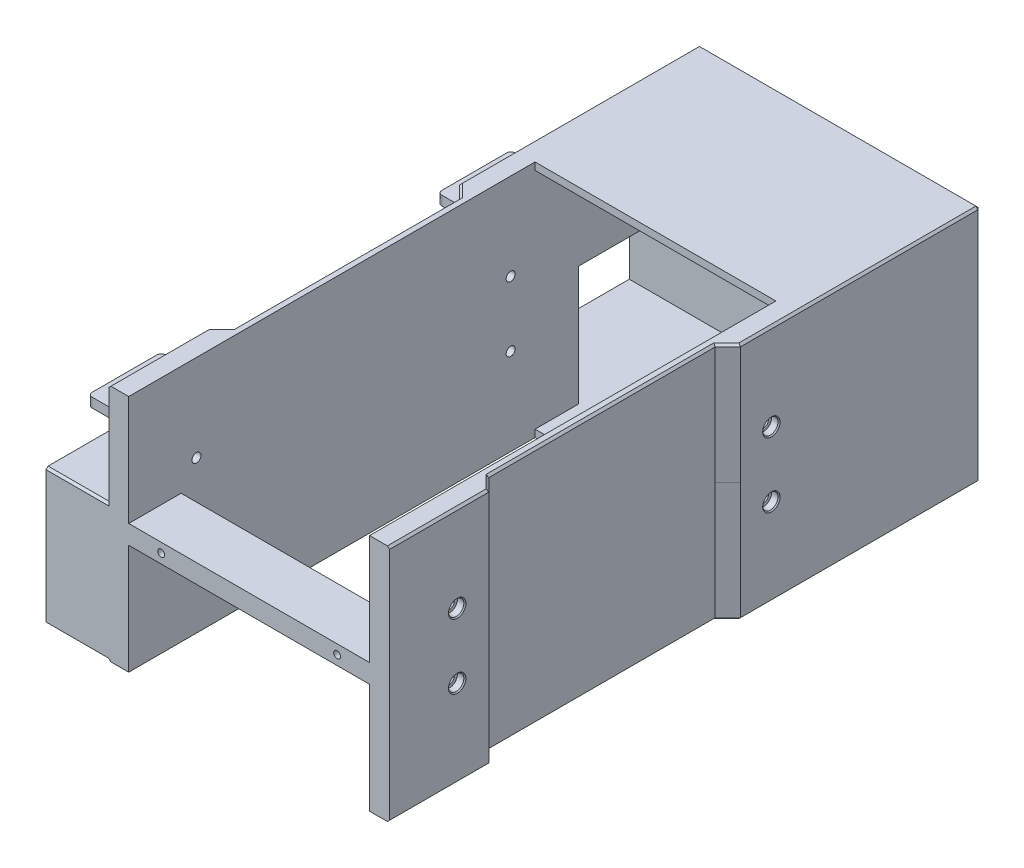
SolidWorks part; units mm, degrees
ref_plane "Front Plane" through (0, 0, 0) normal (0, 0, 1) x (1, 0, 0)
ref_plane "Top Plane" through (0, 0, 0) normal (0, 1, 0) x (1, 0, 0)
ref_plane "Right Plane" through (0, 0, 0) normal (1, 0, 0) x (0, 0, -1)
sketch "Sketch1" plane through (0, 0, 0) normal (0, 0, 1) x (1, 0, 0)
  line L1 (0, 0) -> (134, 0)
  line L2 (0, 0) -> (0, 57)
  line L3 (0, 57) -> (134, 57)
  line L4 (134, 0) -> (134, 57)
  dimension "D1" = 134
  dimension "D2" = 57
extrude "Boss-Extrude1" add sketch "Sketch1" along normal blind 282
sketch "Sketch2" plane through (0, 0, 282) normal (0, 0, 1) x (1, 0, 0)
  line L0 (0, 57) -> (0, 0) construction
  line L1 (9.5, 53.5) -> (124.5, 53.5)
  line L2 (9.5, 53.5) -> (9.5, 0)
  line L3 (9.5, 0) -> (124.5, 0)
  line L4 (124.5, 53.5) -> (124.5, 0)
  line L5 (134, 57) -> (0, 57) construction
  line L6 (134, 0) -> (134, 57) construction
  line L8 (0, 0) -> (134, 0) construction
  dimension "D1" = 9.5
  dimension "D2" = 3.5
  dimension "D3" = 9.5
extrude "Cut-Extrude1" cut sketch "Sketch2" against normal blind 278.5
sketch "Sketch3" plane through (0, 57, 0) normal (0, 1, 0) x (1, 0, 0)
  line L0 (134, -282) -> (0, -282) construction
  line L1 (9.5, -282) -> (124.5, -282)
  line L2 (9.5, -282) -> (9.5, -88)
  line L3 (9.5, -88) -> (124.5, -88)
  line L4 (124.5, -282) -> (124.5, -88)
  line L5 (0, -282) -> (0, 0) construction
  line L6 (134, -282) -> (134, 0) construction
  dimension "D1" = 9.5
  dimension "D2" = 9.5
  dimension "D3" = 194
extrude "Cut-Extrude2" cut sketch "Sketch3" against normal up to surface (3.5 mm away) up to face at (67, 53.5, 142.75)
sketch "Sketch4" plane through (0, 0, 0) normal (0, -1, 0) x (1, 0, 0)
  line L0 (67, 282) -> (67, 0) construction
  line L1 (0, 282) -> (9.5, 282) construction
  line L3 (0, 282) -> (0, 0) construction
  line L4 (0, 234.5) -> (6, 234.5)
  line L5 (0, 234.5) -> (0, 114.5)
  line L6 (0, 114.5) -> (6, 114.5)
  line L7 (6, 234.5) -> (6, 114.5)
  line L8 (128, 234.5) -> (128, 114.5)
  line L9 (134, 114.5) -> (128, 114.5)
  line L10 (134, 234.5) -> (134, 114.5)
  line L11 (134, 234.5) -> (128, 234.5)
  line L12 (0, 0) -> (134, 0) construction
  line L13 (0, 282) -> (9.5, 282) construction
  dimension "D1" = 47.5
  dimension "D2" = 6
  dimension "D3" = 120
extrude "Cut-Extrude3" cut sketch "Sketch4" against normal through all
chamfer "Chamfer1" distance 6 angle 45 4 edges at (6, 28.5, 234.5) (6, 28.5, 114.5) (128, 28.5, 114.5) (128, 28.5, 234.5)
sketch "Sketch5" plane through (134, 0, 0) normal (1, 0, 0) x (0, 0, -1)
  line L0 (-282, 15.5) -> (0, 15.5) construction
  line L4 (-282, 0) -> (-282, 57) construction
  line L5 (0, 0) -> (0, 57) construction
  line L6 (-282, 57) -> (-234.5, 57) construction
  circle A0 centre (-249.65, 15.5) radius 2.15
  circle A1 centre (-99.65, 15.5) radius 2.15
  point P2 (0, 0)
  point P14 (0, 0)
  point P15 (-282, 15.5)
  dimension "D2" = 4.3
  dimension "D4" = 150
  dimension "D1" = 41.5
  dimension "D3" = 32.35
extrude "Cut-Extrude4" cut sketch "Sketch5" against normal blind 134
sketch "Sketch6" plane through (9.5, 0, 0) normal (1, 0, 0) x (0, 0, -1)
  line L0 (-88, 57) -> (-282, 57) construction
  line L1 (-282, 0) -> (-257, 0)
  line L2 (-282, 0) -> (-282, 4.5)
  line L3 (-282, 4.5) -> (-257, 4.5)
  line L4 (-257, 0) -> (-257, 4.5)
  dimension "D1" = 52.5
  dimension "D2" = 25
extrude "Boss-Extrude2" add sketch "Sketch6" along normal blind 115
sketch "Sketch7" plane through (134, 0, 0) normal (1, 0, 0) x (0, 0, -1)
  circle A0 centre (-249.65, 15.5) radius 3.65
  circle A1 centre (-99.65, 15.5) radius 3.65
  dimension "D1" = 7.3
extrude "Cut-Extrude5" cut sketch "Sketch7" against normal blind 3.6
sketch "Sketch8" plane through (0, 0, 0) normal (-1, 0, 0) x (0, 0, 1)
  circle A0 centre (249.65, 15.5) radius 3.65
  circle A1 centre (99.65, 15.5) radius 3.65
  dimension "D1" = 7.3
extrude "Cut-Extrude6" cut sketch "Sketch8" against normal blind 3.6
mirror "Mirror1" about plane through (0, 0, 0) normal (0, 1, 0) of "Cut-Extrude6", "Cut-Extrude5", "Boss-Extrude2", "Cut-Extrude4", "Chamfer1", "Cut-Extrude3", "Cut-Extrude2", "Cut-Extrude1", "Boss-Extrude1"
sketch "Sketch9" plane through (0, 0, 282) normal (0, 0, 1) x (1, 0, 0)
  line L0 (0, 0) -> (134, 0) construction
  line L1 (0, 57) -> (0, -57) construction
  line L2 (134, -57) -> (134, 57) construction
  circle A0 centre (25, 0) radius 1.65
  circle A1 centre (109, 0) radius 1.65
  dimension "D1" = 3.3
  dimension "D2" = 25
  dimension "D3" = 25
extrude "Cut-Extrude7" cut sketch "Sketch9" against normal blind 25
chamfer "Chamfer2" distance 1 angle 45 24 edges at (0, -57, 258.25) (3, -57, 231.5) (6, -57, 174.5) (3, -57, 117.5) (0, 57, 258.25) (3, 57, 231.5) (6, 57, 174.5) (3, 57, 117.5) (134, 57, 258.25) (131, 57, 231.5) (128, 57, 174.5) (131, 57, 117.5) (134, -57, 258.25) (131, -57, 231.5) (128, -57, 174.5) (131, -57, 117.5) (134, -57, 57.25) (67, -57, 0) (134, 0, 0) (134, 57, 57.25) (67, 57, 0) (0, -57, 57.25) (0, 0, 0) (0, 57, 57.25)
chamfer "Chamfer3" distance 0.5 angle 45 8 edges at (134, 15.5, 96) (134, -15.5, 96) (134, 15.5, 246) (134, -15.5, 246) (0, 15.5, 253.3) (0, -15.5, 253.3) (0, -15.5, 103.3) (0, 15.5, 103.3)
sketch "Sketch11" plane through (0, 0, 0) normal (0, 0, -1) x (-1, 0, 0)
  line L0 (-134, 0) -> (0, 0) construction
  line L1 (-134, -56) -> (-134, 56) construction
  line L2 (-67, 0) -> (-67, 14.25)
  line L3 (-67, 14.25) -> (-109.5, 14.25)
  line L4 (-115.5, 8.25) -> (-115.5, -8.25)
  line L5 (-109.5, -14.25) -> (-67, -14.25)
  line L6 (-67, -14.25) -> (-67, 0)
  line L7 (-109.5, 14.25) -> (-115.5, 8.25)
  line L8 (-115.5, -8.25) -> (-109.5, -14.25)
  circle A0 centre (-91.25, -20) radius 1.65
  circle A1 centre (-91.25, 20) radius 1.65
  point P7 (-115.5, -14.25)
  point P8 (-115.5, 14.25)
  dimension "D4" = 3.3
  dimension "D1" = 28.5
  dimension "D2" = 48.5
  dimension "D3" = 18.5
  dimension "D5" = 24.25
  dimension "D8" = 5.75
extrude "Cut-Extrude9" cut sketch "Sketch11" against normal up to surface (3.5 mm away) up to face at (67, 0, 3.5)
sketch "Sketch12" plane through (0, 0, 0) normal (-1, 0, 0) x (0, 0, 1)
  line L0 (57.5429, 57) -> (57.5429, -57) construction
  line L1 (1, 57) -> (114.0858, 57) construction
  line L2 (114.0858, -57) -> (1, -57) construction
  line L3 (258.4571, 57) -> (258.4571, -57) construction
  line L4 (234.9142, 57) -> (282, 57) construction
  line L5 (282, -57) -> (234.9142, -57) construction
  line L6 (0, 8) -> (282, 8) construction
  line L7 (0, -56) -> (0, 56) construction
  line L8 (282, 56) -> (282, -56) construction
  line L9 (0, 8) -> (282, 8)
  line L14 (282, 8) -> (282, -57)
  line L15 (282, -57) -> (278.5, -57)
  line L16 (278.5, -57) -> (278.5, 3.5)
  line L17 (278.5, 3.5) -> (3.5, 3.5)
  line L18 (3.5, 3.5) -> (3.5, -57)
  line L19 (3.5, -57) -> (0, -57)
  line L20 (0, -57) -> (0, 8)
  dimension "D1" = 65
  dimension "D2" = 3.5
  dimension "D3" = 4.5
  dimension "D4" = 3.5
extrude "Boss-Extrude3" add sketch "Sketch12" along normal blind 50 and the other way up to surface (9.5 mm away) other way up to face at (9.5, -17.65, 249.65)
sketch "Sketch14" plane through (0, 0, 0) normal (0, 0, -1) x (-1, 0, 0)
  line L0 (-1, 8) -> (50, 8) construction
  line L1 (50, -57) -> (30, -57)
  line L2 (50, -57) -> (50, 3.5)
  line L3 (50, 3.5) -> (30, 3.5)
  line L4 (30, -57) -> (30, 3.5)
  dimension "D1" = 20
  dimension "D2" = 4.5
extrude "Cut-Extrude10" cut sketch "Sketch14" against normal up to surface (282 mm away) up to face at (57.1176, 4.2353, 282)
sketch "Sketch15" plane through (0, 8, 0) normal (0, 1, 0) x (1, 0, 0)
  line L0 (-50, -282) -> (-50, 0) construction
  line L1 (-50, 0) -> (-30, 0)
  line L2 (-50, 0) -> (-50, -40)
  line L3 (-50, -40) -> (-30, -40)
  line L4 (-30, 0) -> (-30, -40)
  line L5 (-50, -75) -> (-30, -75)
  line L6 (-50, -75) -> (-50, -207)
  line L7 (-50, -207) -> (-30, -207)
  line L8 (-30, -75) -> (-30, -207)
  line L9 (0, -282) -> (-50, -282) construction
  line L10 (-50, -242) -> (-30, -242)
  line L11 (-50, -242) -> (-50, -282)
  line L12 (-50, -282) -> (-30, -282)
  line L13 (-30, -242) -> (-30, -282)
  line L14 (-40, -40) -> (-40, -75) construction
  line L15 (-40, -207) -> (-40, -242) construction
  circle A0 centre (-40, -57.5) radius 2.125
  circle A1 centre (-40, -224.5) radius 2.125
  dimension "D5" = 4.25
  dimension "D1" = 35
  dimension "D2" = 35
  dimension "D3" = 40
  dimension "D4" = 20
extrude "Cut-Extrude11" cut sketch "Sketch15" against normal up to surface (4.5 mm away) up to face at (-17.3333, 3.5, 152.1667)
fillet "Fillet1" radius 2 10 edges at (-15, 3.5, 278.5) (-15, 3.5, 3.5) (-30, 5.75, 40) (-30, 5.75, 207) (-30, 5.75, 75) (-30, 5.75, 242) (-50, 5.75, 242) (-50, 5.75, 207) (-50, 5.75, 40) (-50, 5.75, 75)
chamfer "Chamfer5" distance 1 angle 45 4 edges at (-10.25, -57, 282) (-14.5, 8, 0) (-10.25, -57, 0) (-15, 8, 282)
sketch "Sketch16" plane through (0, 0, 282) normal (0, 0, 1) x (1, 0, 0)
  line L0 (-30, -56) -> (9.5, -56) construction
  line L1 (9.5, -57) -> (0, -57)
  line L2 (9.5, -57) -> (9.5, -56)
  line L3 (9.5, -56) -> (0, -56)
  line L4 (0, -57) -> (0, -56)
  line L5 (0, 56) -> (0, 7) construction
extrude "Boss-Extrude4" add sketch "Sketch16" against normal blind 1
chamfer "Chamfer6" distance 1 angle 45 1 edges at (0, -57, 281.5)
sketch "Sketch17" plane through (0, 0, 0) normal (-1, 0, 0) x (0, 0, 1)
  line L0 (3.5, -57) -> (3.5, 1.5) construction
  line L1 (3.5, -53.5) -> (278.5, -53.5)
  line L2 (3.5, -53.5) -> (3.5, -57)
  line L3 (3.5, -57) -> (278.5, -57)
  line L4 (278.5, -53.5) -> (278.5, -57)
  dimension "D1" = 3.5
extrude "Boss-Extrude5" add sketch "Sketch17" along normal up to surface (30 mm away) and the other way up to surface (9.5 mm away) up to face at (-30, -15.3429, 10.0095) other way up to face at (9.5, -17.65, 249.65)
sketch "Sketch18" plane through (0, 0, 0) normal (-1, 0, 0) x (0, 0, 1)
  line L0 (205, 3.5) -> (77, 3.5) construction
  line L1 (3.5, -53.5) -> (67.15, -53.5)
  line L2 (3.5, -53.5) -> (3.5, 1.5)
  line L3 (5.5, 3.5) -> (67.15, 3.5)
  line L4 (67.15, -53.5) -> (67.15, 3.5)
  arc A0 (3.5, 1.5) -> (5.5, 3.5) centre (5.5, 1.5) cw
  dimension "D2" = 2
  dimension "D1" = 63.65
extrude "Cut-Extrude12" cut sketch "Sketch18" against normal up to surface (9.5 mm away) up to face at (9.5, 0, 166.75)
